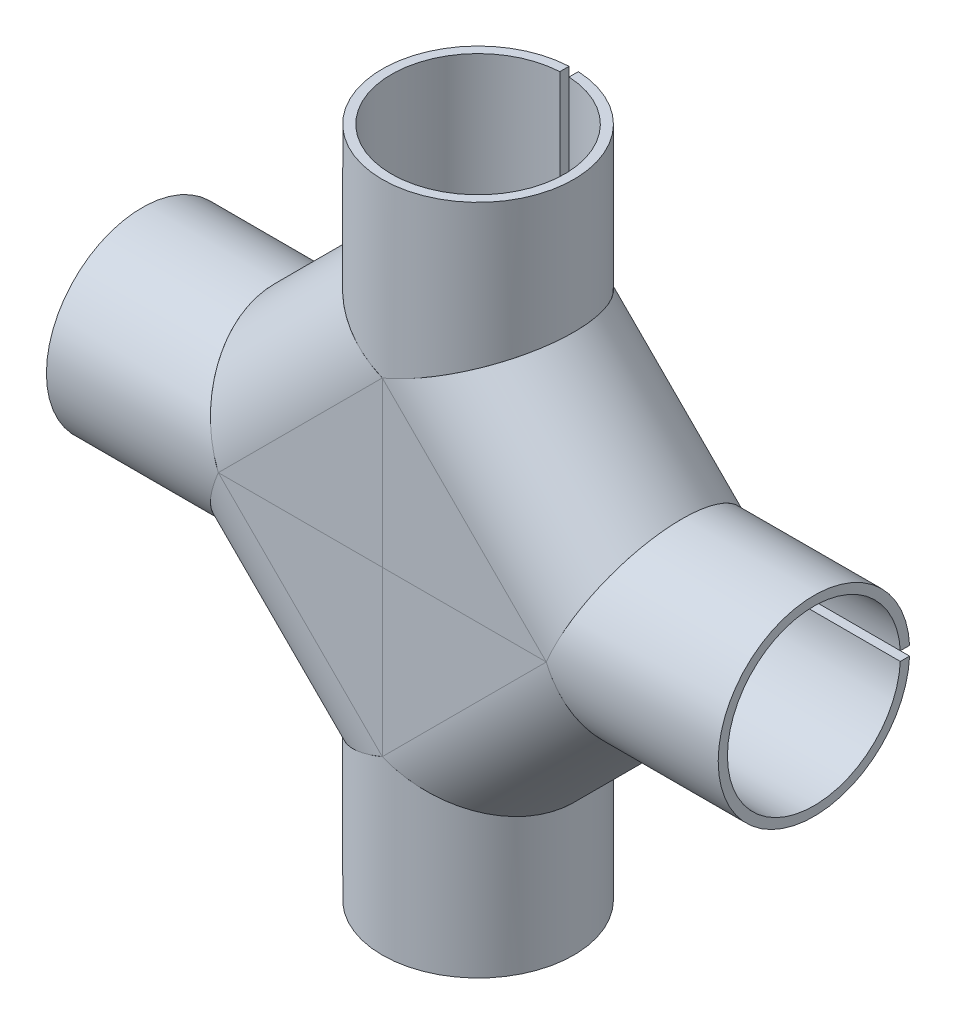
SolidWorks part; units mm, degrees
ref_plane "前视基准面" through (0, 0, 0) normal (0, 0, 1) x (1, 0, 0)
ref_plane "上视基准面" through (0, 0, 0) normal (0, 1, 0) x (1, 0, 0)
ref_plane "右视基准面" through (0, 0, 0) normal (1, 0, 0) x (0, 0, -1)
sketch "草图1" plane through (0, 0, 0) normal (0, 0, 1) x (1, 0, 0)
  line L0 (0, 36.3119) -> (0, -36.3119) construction
  line L1 (-10.3514, 36.3119) -> (10.3514, 36.3119) construction
  line L2 (-36.3119, 0) -> (36.3119, 0) construction
  line L3 (36.3119, 10.3514) -> (36.3119, -10.3514) construction
  line L4 (-36.3119, 10.3514) -> (-36.3119, -10.3514) construction
  line L5 (10.3514, 36.3119) -> (10.3514, 22.016) construction
  line L6 (10.3514, 22.016) -> (22.016, 10.3514) construction
  line L7 (22.016, 10.3514) -> (36.3119, 10.3514) construction
  line L8 (-10.3514, 36.3119) -> (-10.3514, 22.016) construction
  line L9 (-10.3514, 22.016) -> (-22.016, 10.3514) construction
  line L10 (-22.016, 10.3514) -> (-36.3119, 10.3514) construction
  line L11 (-22.016, 10.3514) -> (-17.7283, 0) construction
  line L12 (-17.7283, 0) -> (0, 17.7283) construction
  line L13 (0, 17.7283) -> (17.7283, 0) construction
  line L14 (17.7283, 0) -> (22.016, 10.3514) construction
  line L15 (-10.3514, 22.016) -> (0, 17.7283) construction
  line L16 (0, 17.7283) -> (10.3514, 22.016) construction
  line L17 (8.8641, 8.8641) -> (16.1837, 16.1837) construction
  line L18 (10.3514, 22.016) -> (-10.3514, 22.016) construction
  line L19 (0, 22.016) -> (0, 17.7283) construction
  line L21 (0, -36.3119) -> (0, -37.3119) construction
  line L22 (0, 0) -> (0, 36.3119)
  line L23 (0, 36.3119) -> (10.3514, 36.3119) construction
  dimension "D1" = 45
  dimension "L1" = 36.3119
  dimension "R" = 10.3514
  dimension "L2" = 17.7283
  dimension "t" = 1
sketch "草图2" plane through (0, 0, 0) normal (0, 1, 0) x (1, 0, 0)
  line L0 (0, 10.3514) -> (0, -10.3514) construction
  circle A0 centre (0, 0) radius 10.3514
extrude "拉伸-薄壁1" add sketch "草图2" along normal up to vertex (36.3119 mm away) thin up to point (10.3514, 36.3119, 0) thin type one direction reverse wall 1
ref_plane "基准面1" through (0, 17.7283, 0) normal (0.7071, -0.7071, 0) x (0.7071, 0.7071, 0)
sketch "草图4" plane through (0, 17.7283, 0) normal (0.7071, -0.7071, 0) x (0.7071, 0.7071, 0)
  circle A0 centre (0, 0) radius 10.3514
extrude "拉伸-薄壁3" add sketch "草图4" along normal up to vertex (25.0716 mm away) separate body thin up to point (17.7283, 0, 0) thin type one direction reverse wall 1
ref_plane "基准面2" through (0, 0, 10.3514) normal (0, 0, 1) x (1, 0, 0)
ref_plane "基准面3" through (0, 0, -10.3514) normal (0, 0, 1) x (1, 0, 0)
sketch "草图6" plane through (0, 0, 0) normal (0, 0, 1) x (1, 0, 0)
  line L0 (0, 17.7283) -> (17.7283, 0) construction
  line L1 (0, 17.7283) -> (10.3514, 22.016) construction
  line L2 (17.7283, 0) -> (22.016, 10.3514) construction
  line L3 (10.3514, 22.016) -> (22.016, 10.3514) construction
  line L4 (0, 17.7283) -> (17.7283, 0)
  line L5 (0, 17.7283) -> (10.3514, 22.016)
  line L6 (17.7283, 0) -> (22.016, 10.3514)
  line L7 (10.3514, 22.016) -> (22.016, 10.3514)
extrude "切除-拉伸2" cut sketch "草图6" against normal through all and the other way through all flip side to cut
sketch "草图5" plane through (0, 0, 10.3514) normal (0, 0, 1) x (1, 0, 0)
  line L0 (0, 17.7283) -> (0, 0)
  line L1 (0, 0) -> (17.7283, 0)
  line L2 (17.7283, 0) -> (0, 17.7283)
extrude "凸台-拉伸1" add sketch "草图5" against normal blind 1
sketch "草图7" plane through (0, 0, 0) normal (0, 0, 1) x (1, 0, 0)
  line L0 (0, 17.7283) -> (10.3514, 22.016) construction
  line L1 (-10.3514, 22.016) -> (0, 17.7283) construction
  line L2 (-10.3514, 36.3119) -> (-10.3514, 22.016) construction
  line L3 (10.3514, 36.3119) -> (10.3514, 22.016) construction
  line L4 (-10.3514, 36.3119) -> (10.3514, 36.3119) construction
  line L5 (0, 17.7283) -> (10.3514, 22.016)
  line L6 (-10.3514, 22.016) -> (0, 17.7283)
  line L7 (-10.3514, 36.3119) -> (-10.3514, 22.016)
  line L8 (10.3514, 36.3119) -> (10.3514, 22.016)
  line L9 (-10.3514, 36.3119) -> (10.3514, 36.3119)
extrude "切除-拉伸3" cut sketch "草图7" against normal through all and the other way through all flip side to cut
extrude "切除-拉伸-薄壁1" cut sketch "草图1" against normal through all thin thin type mid plane wall 1
ref_axis "基准轴1" through (0, 0, 11.3865) along (0, 0, -1)
mirror "镜向1" about plane through (0, 0, 0) normal (0, 0, 1) of "凸台-拉伸1"
pattern_circular "阵列(圆周)1" count 4 over 360 about axis through (0, 0, 11.3865) along (0, 0, -1) of bodies 114 107 104
equation "\"D5@拉伸-薄壁1\" = \"t@草图1\""
equation "\"D1@凸台-拉伸1\" = \"t@草图1\""
